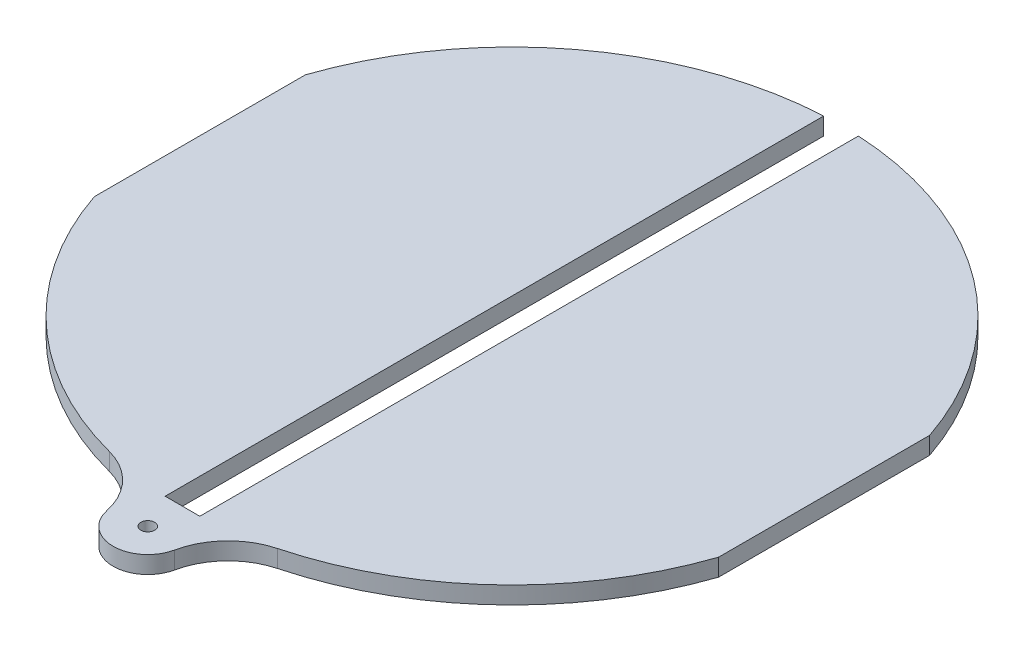
SolidWorks part; units mm, degrees
ref_plane "Front Plane" through (0, 0, 0) normal (0, 0, 1) x (1, 0, 0)
ref_plane "Top Plane" through (0, 0, 0) normal (0, 1, 0) x (1, 0, 0)
ref_plane "Right Plane" through (0, 0, 0) normal (1, 0, 0) x (0, 0, -1)
sketch "Sketch2" plane through (0, 0, 0) normal (0, 1, 0) x (1, 0, 0)
  line L0 (3.175, 63.5) -> (57.15, 63.5)
  line L1 (-57.15, -63.5) -> (-6.35, -63.5)
  line L2 (-57.15, -63.5) -> (-57.15, 63.5)
  line L3 (-57.15, 63.5) -> (-3.175, 63.5)
  line L4 (57.15, -63.5) -> (57.15, 63.5)
  line L5 (-57.15, -63.5) -> (57.15, 63.5) construction
  line L6 (-57.15, 63.5) -> (57.15, -63.5) construction
  line L7 (-3.175, -57.15) -> (3.175, -57.15)
  line L8 (-3.175, -57.15) -> (-3.175, 63.5)
  line L10 (3.175, -57.15) -> (3.175, 63.5)
  line L11 (-3.175, -57.15) -> (3.175, 63.5) construction
  line L12 (-3.175, 63.5) -> (3.175, -57.15) construction
  line L13 (6.35, -63.5) -> (57.15, -63.5)
  arc A0 (-6.35, -63.5) -> (6.35, -63.5) centre (0, -63.5) ccw
  point P0 (0, 0)
  point P6 (0, 3.175)
  dimension "D1" = 127
  dimension "D2" = 114.3
  dimension "D3" = 6.35
  dimension "D4" = 120.65
extrude "Boss-Extrude1" add sketch "Sketch2" along normal blind 3.175 contours L3 L8 L7 L10 L0 L4 L13 A0 L1 L2
sketch "Sketch3" plane through (0, 3.175, 0) normal (0, 1, 0) x (1, 0, 0)
  circle A0 centre (0, -63.5) radius 1.27
  dimension "D1" = 2.54
extrude "Cut-Extrude1" cut sketch "Sketch3" against normal through all
sketch "Sketch4" plane through (0, 3.175, 0) normal (0, 1, 0) x (1, 0, 0)
  line L0 (-3.175, 3.175) -> (83.1266, 3.175) construction
  line L2 (-3.175, -57.15) -> (-3.175, 63.5) construction
  line L7 (0, 0) -> (0, 96.6328) construction
  line L8 (3.175, 63.5) -> (57.15, 63.5) construction
  line L9 (-6.35, -63.5) -> (-6.35, -56.8149)
  line L10 (-57.15, 63.5) -> (57.15, 63.5)
  line L11 (-57.15, 63.5) -> (-57.15, 22.4878)
  line L12 (-57.15, -63.5) -> (-6.35, -63.5)
  line L13 (57.15, 63.5) -> (57.15, 22.4878)
  line L14 (6.35, -63.5) -> (6.35, -56.8149)
  line L15 (57.15, -16.1378) -> (57.15, -63.5)
  line L16 (-57.15, -16.1378) -> (-57.15, -63.5)
  line L17 (6.35, -63.5) -> (57.15, -63.5)
  arc A1 (-57.15, -16.1378) -> (-6.35, -56.8149) centre (0, 3.175) ccw
  arc A2 (57.15, 22.4878) -> (-57.15, 22.4878) centre (0, 3.175) ccw
  arc A3 (6.35, -56.8149) -> (57.15, -16.1378) centre (0, 3.175) ccw
  line M11 (-57.15, 63.5) -> (-57.15, -63.5)
  line M12 (-57.15, -63.5) -> (-6.35, -63.5)
  line M14 (6.35, -63.5) -> (57.15, -63.5)
  line M15 (57.15, -63.5) -> (57.15, 63.5)
  line M16 (57.15, 63.5) -> (3.175, 63.5)
  line M17 (3.175, 63.5) -> (3.175, -57.15)
  line M19 (-3.175, -57.15) -> (-3.175, 63.5)
  line M20 (-3.175, 63.5) -> (-57.15, 63.5)
extrude "Cut-Extrude2" cut sketch "Sketch4" against normal through all both and the other way through all contours A1 L9 M11 M12 | A2 M19 M20 M11 | A3 L14 M14 M15 | A2 M15 M16 M17 region at (-39.8759, 3.175, 50.9526) region at (39.8759, 3.175, 50.9526) region at (-43.9996, 3.175, -52.513) region at (43.9996, 3.175, -52.513)
fillet "Fillet1" radius 12.7 2 edges at (6.35, 1.5875, 56.8149) (-6.35, 1.5875, 56.8149)
